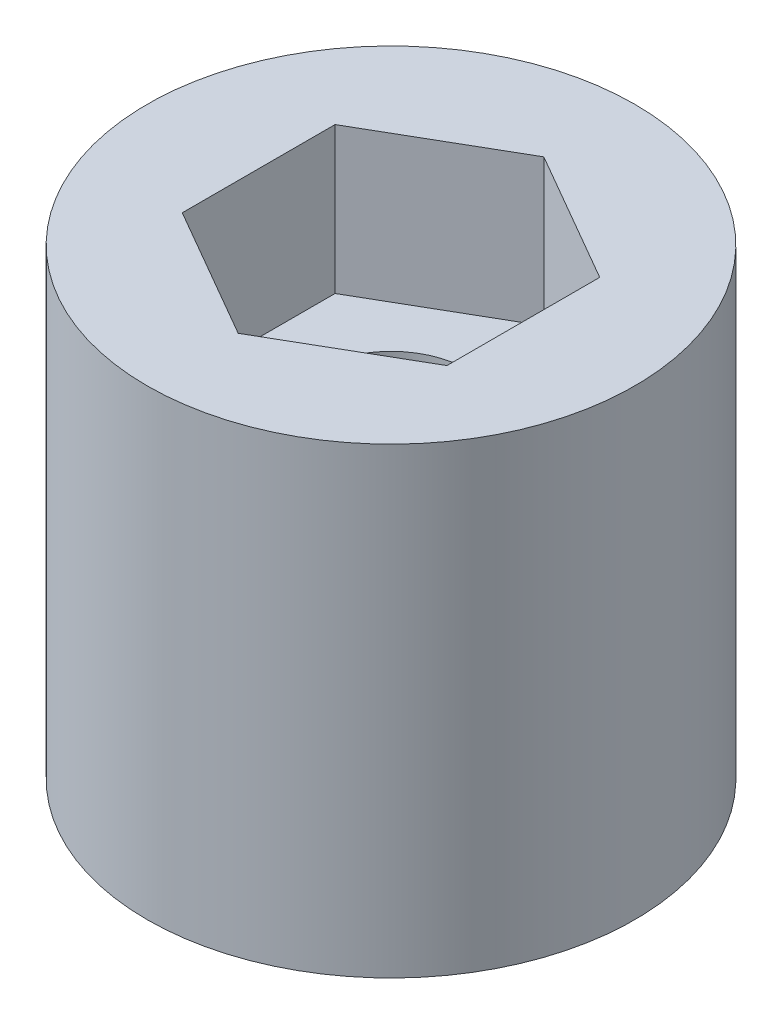
SolidWorks part; units mm, degrees
ref_plane "Front Plane" through (0, 0, 0) normal (0, 0, 1) x (1, 0, 0)
ref_plane "Top Plane" through (0, 0, 0) normal (0, 1, 0) x (1, 0, 0)
ref_plane "Right Plane" through (0, 0, 0) normal (1, 0, 0) x (0, 0, -1)
sketch "Sketch1" plane through (0, 0, 0) normal (0, 1, 0) x (1, 0, 0)
  circle A0 centre (0, 0) radius 5
  circle A1 centre (0, 0) radius 1.575
  dimension "D1" = 10
  dimension "D2" = 3.15
extrude "Boss-Extrude1" add sketch "Sketch1" along normal blind 9.48
sketch "Sketch2" plane through (0, 9.48, 0) normal (0, 1, 0) x (1, 0, 0)
  line L1 (0, 3.1333) -> (-2.7135, 1.5666)
  line L2 (-2.7135, 1.5666) -> (-2.7135, -1.5666)
  line L3 (-2.7135, -1.5666) -> (0, -3.1333)
  line L4 (0, -3.1333) -> (2.7135, -1.5666)
  line L5 (2.7135, -1.5666) -> (2.7135, 1.5666)
  line L6 (2.7135, 1.5666) -> (0, 3.1333)
  circle A0 centre (0, 0) radius 2.7135 construction
  point P1 (0.3974, 3.108)
  point P10 (0, 3.1333)
  circle M2 centre (0, 0) radius 1.575
  dimension "D1" = 5.427
extrude "Cut-Extrude1" cut sketch "Sketch2" against normal blind 3 contours L5 L6 L1 L2 L3 L4 M2 region at (1.3153, 9.48, -2.2782)
equation "\"bearing_21_OD\"= 21mm"
equation "\"pin_cirlce_diameter\"= 75mm"
equation "\"pin_diam\"= 6mm"
equation "\"gear_thickness\"= 4mm"
equation "\"ball_bearing_diam\"= 2.96mm"
equation "\"bearing_21_outer_clearance\"= 0mm'change this"
equation "\"bearing_15_OD\"= 15mm"
equation "\"bearing_15_outer_clearance\"= 0mm'change this"
equation "\"thrust_bearing_thickness\"= 5mm'measure this irl and change"
equation "\"D1@Boss-Extrude1\"=\"gear_thickness\"*2+0.5*\"ball_bearing_diam\""
